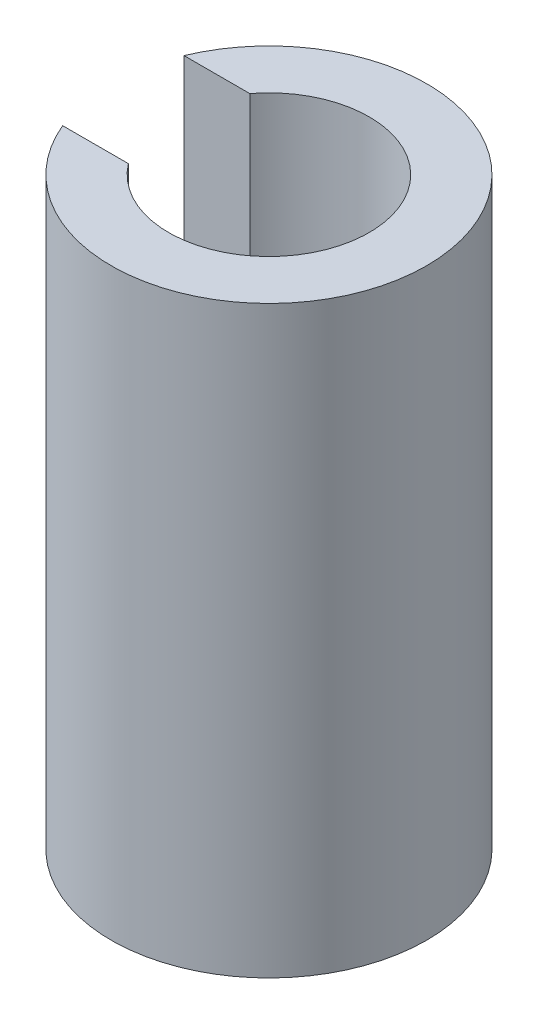
SolidWorks part; units mm, degrees
ref_plane "前基準面" through (0, 0, 0) normal (0, 0, 1) x (1, 0, 0)
ref_plane "上基準面" through (0, 0, 0) normal (0, 1, 0) x (1, 0, 0)
ref_plane "右基準面" through (0, 0, 0) normal (1, 0, 0) x (0, 0, -1)
ref_axis "基準軸1" through (0, -55, 0) along (0, 1, 0)
ref_axis "基準軸2" through (-88.99, 0, 0) along (1, 0, 0)
ref_axis "基準軸3" through (0, 0, 55) along (0, 0, -1)
sketch "草圖1" plane through (0, 0, 0) normal (0, 1, 0) x (1, 0, 0)
  circle A0 centre (0, 0) radius 2.575
  circle A1 centre (0, 0) radius 4.05
  dimension "D1" = 5.15
  dimension "D2" = 8.1
extrude "填料-伸長1" add sketch "草圖1" along normal blind 15
sketch "草圖2" plane through (0, 15, 0) normal (0, 1, 0) x (1, 0, 0)
  line L1 (-4.05, -1.5582) -> (-2.05, -1.5582)
  line L2 (-4.05, -1.5582) -> (-4.05, 1.5582)
  line L3 (-4.05, 1.5582) -> (-2.05, 1.5582)
  line L4 (-2.05, -1.5582) -> (-2.05, 1.5582)
  line L5 (-55, 0) -> (55, 0) construction
  circle A0 centre (0, 0) radius 4.05 construction
  circle A1 centre (0, 0) radius 2.575 construction
  point P4 (-2.05, 0)
  dimension "D1" = 2
extrude "除料-伸長1" cut sketch "草圖2" against normal blind 15
